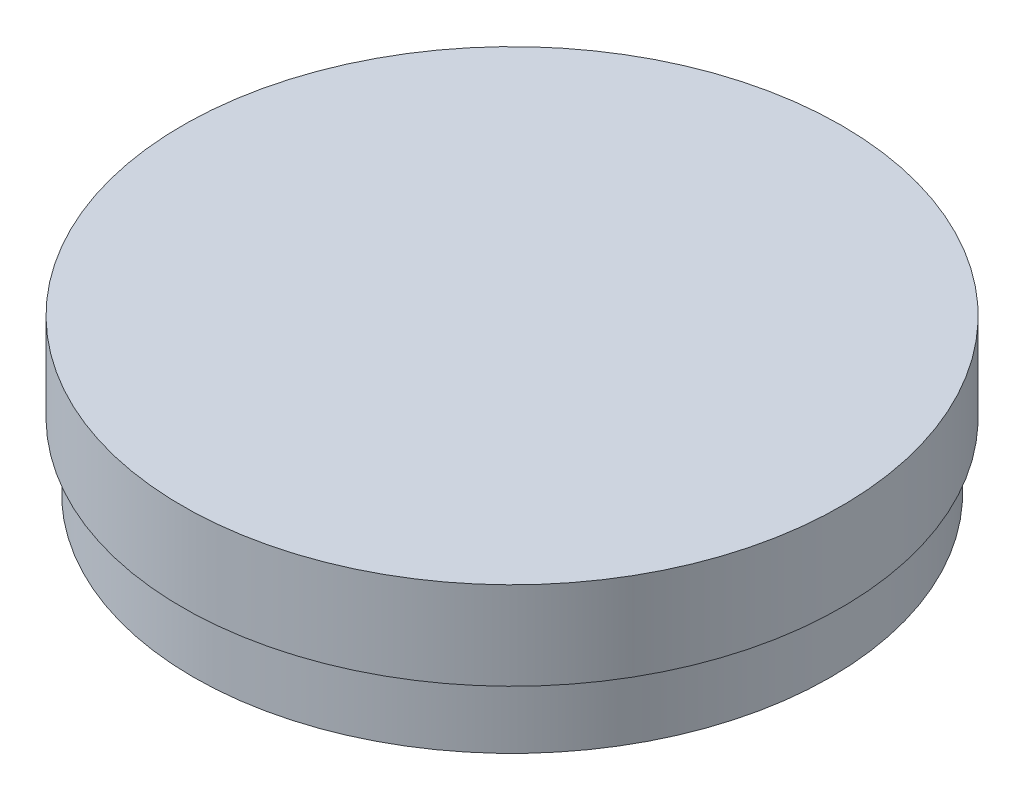
SolidWorks part; units mm, degrees
material "Polyethylene Cross-Linked"
ref_plane "Front Plane" through (0, 0, 0) normal (0, 0, 1) x (1, 0, 0)
ref_plane "Top Plane" through (0, 0, 0) normal (0, 1, 0) x (1, 0, 0)
ref_plane "Right Plane" through (0, 0, 0) normal (1, 0, 0) x (0, 0, -1)
sketch "Sketch1" plane through (0, 0, 0) normal (0, 0, 1) x (1, 0, 0)
  line L0 (0, 0) -> (0, 92.3285) construction
  line L1 (0, 0) -> (92.075, 0)
  line L2 (92.075, 0) -> (92.075, 19.05)
  line L3 (92.075, 19.05) -> (95.25, 19.05)
  line L4 (95.25, 19.05) -> (95.25, 44.45)
  line L5 (95.25, 44.45) -> (0, 44.45)
  line L6 (0, 44.45) -> (0, 0)
  dimension "D1" = 95.25
  dimension "D2" = 3.175
  dimension "D3" = 19.05
  dimension "D4" = 25.4
revolve "Revolve1" add sketch "Sketch1" angle 360 about L0
ref_plane "Plane1" through (0, 0, 101) normal (0, 0, 1) x (1, 0, 0)
ref_plane "Plane2" through (92.075, 0, 0) normal (1, 0, 0) x (0, 0, -1)
shell "Shell1" thickness 12.7 removed face at (0, 0, -92.075)
